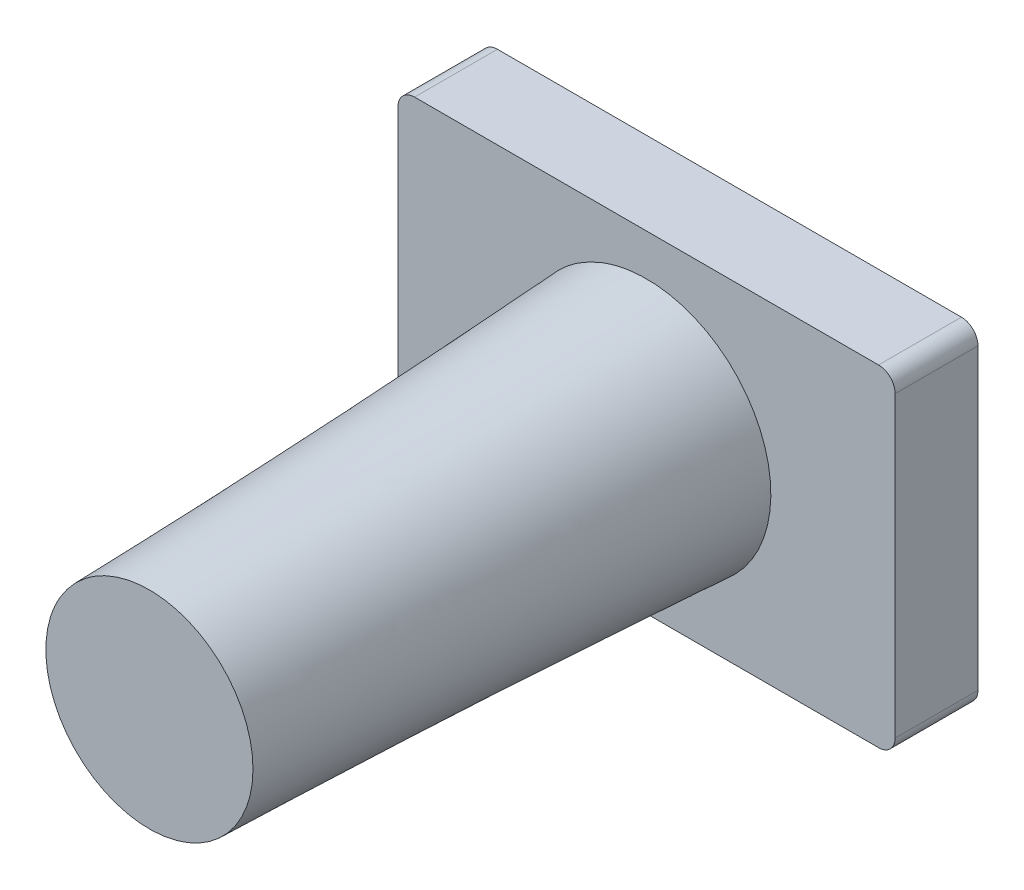
SolidWorks part; units mm, degrees
ref_plane "Front Plane" through (0, 0, 0) normal (0, 0, 1) x (1, 0, 0)
ref_plane "Top Plane" through (0, 0, 0) normal (0, 1, 0) x (1, 0, 0)
ref_plane "Right Plane" through (0, 0, 0) normal (1, 0, 0) x (0, 0, -1)
sketch "Sketch4" plane through (0, 0, 0) normal (0, 1, 0) x (1, 0, 0)
  line L1 (-280, 200) -> (280, 200)
  line L2 (-300, 180) -> (-300, -180)
  line L3 (-280, -200) -> (280, -200)
  line L4 (300, 180) -> (300, -180)
  line L5 (-300, 200) -> (300, -200) construction
  line L6 (-300, -200) -> (300, 200) construction
  arc A0 (-300, -180) -> (-280, -200) centre (-280, -180) ccw
  arc A1 (280, -200) -> (300, -180) centre (280, -180) ccw
  arc A2 (280, 200) -> (300, 180) centre (280, 180) cw
  arc A3 (-280, 200) -> (-300, 180) centre (-280, 180) ccw
  point P0 (0, 0)
  dimension "D3" = 20
  dimension "D1" = 600
  dimension "D2" = 400
extrude "Boss-Extrude3" add sketch "Sketch4" along normal blind 100
sketch "Sketch6" plane through (0, 100, 0) normal (0, 1, 0) x (1, 0, 0)
  circle A0 centre (0, 0) radius 150
  dimension "D1" = 300
ref_plane "Plane1" through (0, 700, 0) normal (0, 1, 0) x (1, 0, 0)
sketch "Sketch7" plane through (0, 700, 0) normal (0, 1, 0) x (1, 0, 0)
  circle A0 centre (0, 0) radius 125
  dimension "D1" = 250
loft "Loft1" add profiles "Sketch7", "Sketch6" connector at (94.5388, 700, 81.7766) connector at (67.7625, 100, 133.8217)
move or copy body "Body-Move/Copy2" bodies to move or copy 105 copy no rotation origin (0, 0, 0) rotation axis (1, 0, 0) rotation angle 90
